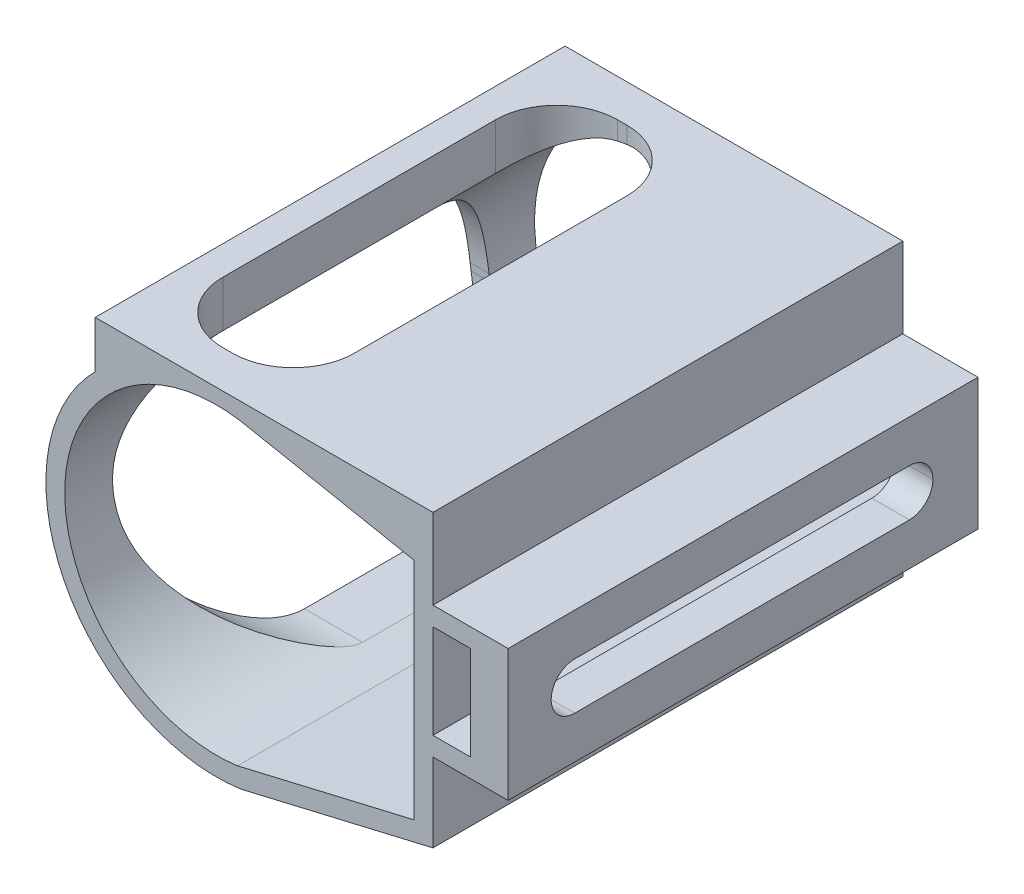
SolidWorks part; units mm, degrees
ref_plane "Alzado" through (0, 0, 0) normal (0, 0, 1) x (1, 0, 0)
ref_plane "Planta" through (0, 0, 0) normal (0, 1, 0) x (1, 0, 0)
ref_plane "Vista lateral" through (0, 0, 0) normal (1, 0, 0) x (0, 0, -1)
sketch "Croquis2" plane through (0, 0, 0) normal (0, 0, 1) x (1, 0, 0)
  line L0 (-51.9511, -1.694) -> (-49.9511, -1.694)
  line L1 (-49.9511, -1.694) -> (-51.9511, -1.694)
  line L2 (-1.9511, -10.694) -> (-1.9511, -41.694)
  line L3 (-1.9511, -41.694) -> (-51.9511, -41.694) construction
  line L4 (-51.9511, -1.694) -> (-51.9511, -41.694) construction
  line L5 (-49.9511, -1.694) -> (-49.9511, -11.294)
  line L6 (-49.9511, -11.294) -> (-36.9511, -11.294)
  line L7 (-36.9511, -11.294) -> (-36.9511, -9.294)
  line L8 (-36.9511, -9.294) -> (-31.9511, -9.294)
  line L9 (-31.9511, -9.294) -> (-31.9511, -11.994)
  line L10 (-31.9511, -11.994) -> (-17.3111, -11.994)
  line L11 (-17.3111, -11.994) -> (-17.3111, -7.694)
  line L12 (-17.3111, -7.694) -> (-24.3111, -7.694)
  line L13 (-24.3111, -7.694) -> (-24.3111, -4.694)
  line L14 (-24.3111, -4.694) -> (-14.3111, -4.694)
  line L15 (-14.3111, -4.694) -> (-14.3111, -10.694)
  line L16 (-14.3111, -10.694) -> (-1.9511, -10.694)
  line L17 (-1.9511, -41.694) -> (-4.5642, -41.694)
  line L18 (-4.5642, -41.694) -> (-4.5642, -19.454)
  line L19 (-4.5642, -19.454) -> (-22.3242, -19.454) construction
  line L20 (-22.3242, -41.694) -> (-22.3242, -15.394) construction
  line L21 (-4.5642, -19.454) -> (-22.3242, -15.394)
  line L22 (-42.1842, -30.694) -> (-40.1642, -30.694)
  line L23 (-22.3242, -15.394) -> (-26.7442, -15.394) construction
  line L24 (-42.1842, -41.694) -> (-42.1842, -30.694) construction
  line L25 (-40.1642, -41.694) -> (-40.1642, -30.694) construction
  line L26 (-26.7442, -15.394) -> (-26.7442, -15.354)
  line L27 (-22.3242, -15.394) -> (-26.7442, -15.354)
  line L28 (-40.1642, -30.694) -> (-26.7442, -15.354) construction
  arc A0 (-40.1642, -30.694) -> (-26.7442, -15.354) centre (-26.4173, -29.1801) cw
  dimension "D1" = 2
  dimension "D2" = 50
  dimension "D3" = 40
  dimension "D4" = 9.6
  dimension "D5" = 13
  dimension "D6" = 2
  dimension "D7" = 5
  dimension "D8" = 2.7
  dimension "D9" = 14.64
  dimension "D10" = 4.3
  dimension "D11" = 3
  dimension "D12" = 10
  dimension "D13" = 6
  dimension "D14" = 12.36
  dimension "D15" = 22.24
  dimension "D16" = 17.76
  dimension "D17" = 26.3
  dimension "D18" = 35.6
  dimension "D19" = 2.02
  dimension "D20" = 11
  dimension "D21" = 4.42
  dimension "D22" = 0.04
sketch "Croquis3" plane through (0, 0, 0) normal (0, 0, 1) x (1, 0, 0)
  line L147 (-42.0992, 8.245) -> (-6.1572, 8.245)
  line L218 (-8.1572, 2.8211) -> (-26.7313, 6.4418)
  line L219 (-8.1572, 2.8211) -> (-8.1572, -21.0951)
  line L220 (-8.1572, -21.0951) -> (-26.9615, -25.5138)
  line L238 (-6.1572, -22.6796) -> (-26.591, -27.4812)
  line L239 (-6.1572, 4.4689) -> (-6.1572, -22.6796) construction
  line L241 (-6.1572, 8.245) -> (-6.1572, -22.6796)
  line L242 (-42.0992, 8.245) -> (-42.0992, 3.245)
  line L277 (-6.1572, 4.4689) -> (-26.3861, 8.4121) construction
  arc A14 (-26.9615, -25.5138) -> (-26.7313, 6.4418) centre (-29.1957, -9.5191) cw
  arc A17 (-26.591, -27.4812) -> (-42.0992, 3.245) centre (-29.1957, -9.5191) cw
  arc A21 (-26.591, -27.4812) -> (-26.3861, 8.4121) centre (-29.1957, -9.5191) cw construction
  dimension "D18" = 18.8042
  dimension "D15" = 18.574
  dimension "D3" = 5
  dimension "D29" = 16.15
  dimension "D9" = 2
  dimension "D21" = 23.9161
extrude "Saliente-Extruir1" add sketch "Croquis3" along normal blind 50 contours L241 L238 A17 L242 L147 | A14 L218 L219 L220
sketch "Croquis11" plane through (0, 0, 0) normal (0, 0, -1) x (-1, 0, 0)
  line L2 (-1.8428, -14.3028) -> (-1.8428, -0.3028)
  line L3 (-1.8428, -0.3028) -> (6.1572, -0.3028)
  line L4 (6.1572, -0.3028) -> (6.1572, -2.3028)
  line L5 (6.1572, -2.3028) -> (2.1572, -2.3028)
  line L6 (2.1572, -2.3028) -> (2.1572, -12.3028)
  line L7 (2.1572, -12.3028) -> (6.1572, -12.3028)
  line L8 (6.1572, -12.3028) -> (6.1572, -14.3028)
  line L9 (-1.8428, -14.3028) -> (6.1572, -14.3028)
  line L14 (2.1572, -7.3028) -> (3.8938, -7.3028) construction
  dimension "D1" = 8
  dimension "D2" = 2
  dimension "D3" = 2
  dimension "D4" = 14
  dimension "D5" = 4
extrude "Saliente-Extruir2" add sketch "Croquis11" along direction (0, 0, -1) on the side against the normal up to surface (50 mm away) contours L9 L8 L7 L6 L5 L4 L3 L2 up to face at (-22.1265, -9.3032, 50)
sketch "Croquis12" plane through (1.8428, 0, 0) normal (1, 0, 0) x (0, 0, -1)
  line L0 (-45.4229, -7.3028) -> (-43.4878, -7.3028) construction
  line L2 (0, -7.3028) -> (-1.743, -7.3028) construction
  line L4 (0, -0.3028) -> (0, -14.3028) construction
  line L5 (-25, -9.8028) -> (-4.8, -9.8028)
  line L8 (-4.8, -4.8028) -> (-45.4229, -4.8028)
  line L9 (-45.4229, -4.8028) -> (-45.4229, -9.8028)
  line L10 (-45.4229, -9.8028) -> (-25, -9.8028)
  line L11 (-4.8, -9.8028) -> (-4.8, -4.8028)
  dimension "D3" = 5
extrude "Cortar-Extruir12" cut sketch "Croquis12" against normal up to surface (10 mm away) contours L11 L8 L9 L10 L5 up to face at (-8.1572, -9.137, 25)
fillet "Redondeo1" radius 2.5 8 edges at (-0.1572, -4.8028, 4.8) (-0.1572, -9.8028, 4.8) (-0.1572, -9.8028, 45.4229) (-0.1572, -4.8028, 45.4229) (-7.1572, -9.8028, 4.8) (-7.1572, -4.8028, 4.8) (-7.1572, -9.8028, 45.4229) (-7.1572, -4.8028, 45.4229)
ref_plane "Plano1" through (-48.1572, 0, 0) normal (-1, 0, 0) x (0, 0, 1)
sketch "Croquis16" plane through (-48.1572, 0, 0) normal (-1, 0, 0) x (0, 0, 1)
  line L0 (32, -25.4812) -> (18, -25.4812)
  line L2 (25, 5.245) -> (25, 1.245) construction
  line L3 (50, 5.245) -> (0, 5.245) construction
  line L9 (5, -11.755) -> (5, -12.4812)
  line L10 (32, 1.245) -> (18, 1.245)
  line L11 (45, -12.4812) -> (45, -11.755)
  line L16 (5, -12.1181) -> (45, -12.1181) construction
  arc A0 (32, 1.245) -> (45, -11.755) centre (32, -11.755) cw
  arc A3 (5, -11.755) -> (18, 1.245) centre (18, -11.755) cw
  arc A4 (32, -25.4812) -> (45, -12.4812) centre (32, -12.4812) ccw
  arc A5 (5, -12.4812) -> (18, -25.4812) centre (18, -12.4812) ccw
  point P0 (25, 5.245)
  dimension "D2" = 7
  dimension "D1" = 4
extrude "Cortar-Extruir17" cut sketch "Croquis16" against normal up to surface (16.5053 mm away) up to face at (-36.0958, -9.4694, 25)
sketch "Croquis18" plane through (0, 8.245, 0) normal (0, 1, 0) x (1, 0, 0)
  line L0 (-28.5072, -4) -> (-28.5072, 0) construction
  line L1 (-25.0072, -46) -> (-32.0072, -46)
  line L2 (-25.0072, -46) -> (-25.0072, -4)
  line L3 (-25.0072, -4) -> (-32.0072, -4)
  line L8 (-15.1572, 0) -> (-41.8572, 0) construction
  line L9 (-15.1572, -50) -> (-15.1572, 0) construction
  line L10 (-41.8572, -50) -> (-15.1572, -50) construction
  line L11 (-41.8572, 0) -> (-41.8572, -50) construction
  line L12 (-32.0072, -46) -> (-32.0072, -4)
  point P8 (-28.5072, -4)
  point P9 (-28.5072, 0)
  dimension "D2" = 4
  dimension "D3" = 4
  dimension "D4" = 7
extrude "Cortar-Extruir19" cut sketch "Croquis18" against normal up to next
sketch "Croquis22" plane through (0, 8.245, 0) normal (0, 1, 0) x (1, 0, 0)
  line L6 (-32.0072, -4) -> (-39.0072, -4)
  line L7 (-32.0072, -4) -> (-32.0072, -46)
  line L8 (-32.0072, -46) -> (-39.0072, -46)
  line L9 (-39.0072, -4) -> (-39.0072, -46)
  dimension "D1" = 7
extrude "Cortar-Extruir22" cut sketch "Croquis22" against normal up to next
fillet "Redondeo10" radius 6.5 4 edges at (-39.0072, 5.777, 4) (-25.0072, 7.1754, 4) (-39.0072, 5.777, 46) (-25.0072, 7.1754, 46)
